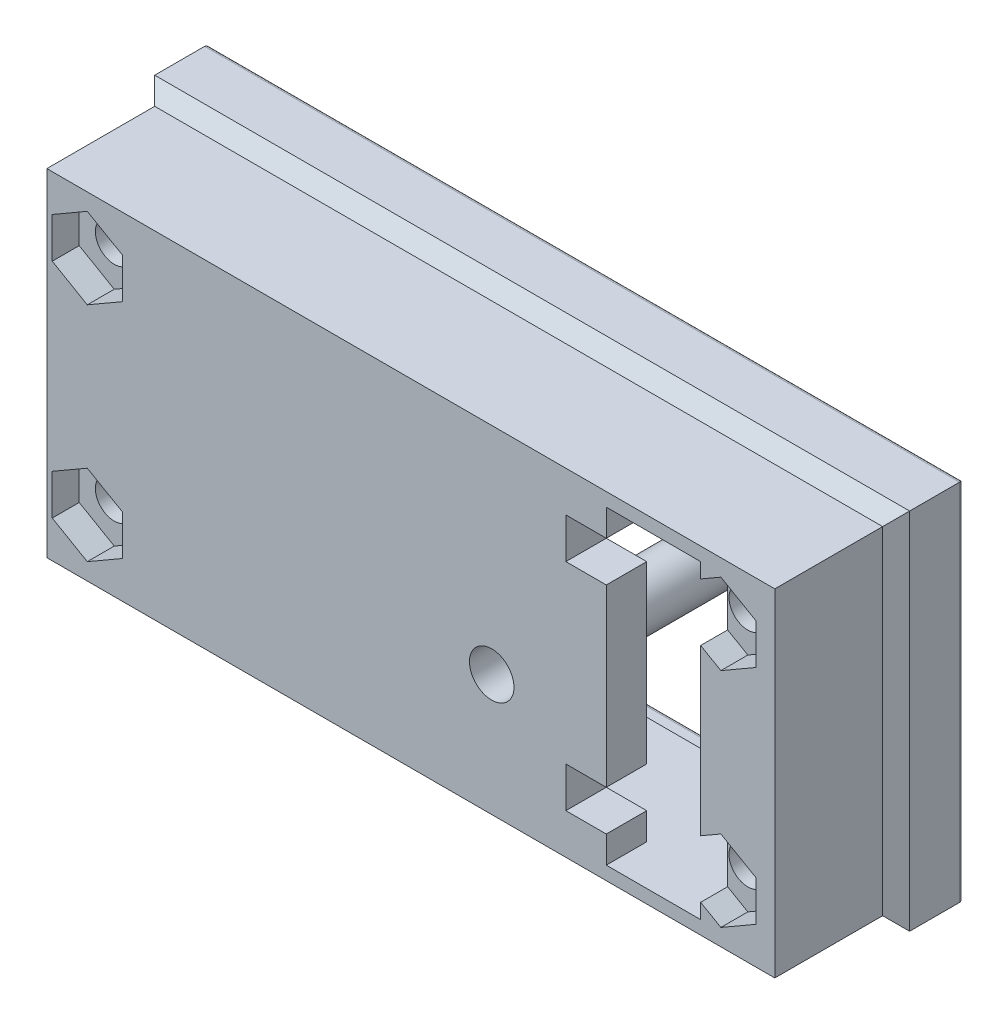
SolidWorks part; units mm, degrees
ref_plane "Front Plane" through (0, 0, 0) normal (0, 0, 1) x (1, 0, 0)
ref_plane "Top Plane" through (0, 0, 0) normal (0, 1, 0) x (1, 0, 0)
ref_plane "Right Plane" through (0, 0, 0) normal (1, 0, 0) x (0, 0, -1)
sketch "Sketch1" plane through (0, 0, 0) normal (0, 0, 1) x (1, 0, 0)
  line L1 (27, -12.5) -> (-27, -12.5)
  line L2 (27, -12.5) -> (27, 12.5)
  line L3 (27, 12.5) -> (-27, 12.5)
  line L4 (-27, -12.5) -> (-27, 12.5)
  line L5 (27, -12.5) -> (-27, 12.5) construction
  line L6 (27, 12.5) -> (-27, -12.5) construction
  line L7 (26, -11.5) -> (-26, -11.5)
  line L8 (26, -11.5) -> (26, 11.5)
  line L9 (26, 11.5) -> (-26, 11.5)
  line L10 (-26, -11.5) -> (-26, 11.5)
  line L11 (26, -11.5) -> (-26, 11.5) construction
  line L12 (26, 11.5) -> (-26, -11.5) construction
  point P0 (0, 0)
  point P6 (0, 0)
  dimension "D1" = 52
  dimension "D2" = 23
  dimension "D3" = 1
  dimension "D4" = 1
extrude "Boss-Extrude1" add sketch "Sketch1" along normal blind 8
sketch "Sketch2" plane through (0, 0, 8) normal (0, 0, 1) x (1, 0, 0)
  line L1 (27, -12.5) -> (-27, -12.5)
  line L2 (27, -12.5) -> (27, 12.5)
  line L3 (27, 12.5) -> (-27, 12.5)
  line L4 (-27, -12.5) -> (-27, 12.5)
  line L5 (27, -12.5) -> (-27, 12.5) construction
  line L6 (27, 12.5) -> (-27, -12.5) construction
  point P0 (0, 0)
extrude "Boss-Extrude2" add sketch "Sketch2" along normal blind 3
sketch "Sketch4" plane through (0, 0, 8) normal (0, 0, -1) x (-1, 0, 0)
  line L0 (26, -11.5) -> (-26, -11.5) construction
  line L1 (-21.5, 11.5) -> (-14.5, 11.5)
  line L2 (-21.5, 11.5) -> (-21.5, -11.5)
  line L3 (-21.5, -11.5) -> (-14.5, -11.5)
  line L4 (-14.5, 11.5) -> (-14.5, -11.5)
  line L5 (26, 11.5) -> (26, -11.5) construction
  line L6 (-26, 11.5) -> (26, 11.5) construction
  dimension "D1" = 7
  dimension "D2" = 40.5
extrude "Cut-Extrude1" cut sketch "Sketch4" against normal blind 3
sketch "Sketch5" plane through (0, 0, 8) normal (0, 0, -1) x (-1, 0, 0)
  circle A0 centre (-10, 0) radius 2
  dimension "D1" = 4
  dimension "D2" = 10
extrude "Boss-Extrude3" add sketch "Sketch5" along normal blind 9.7
fillet "Fillet1" radius 2 1 edges at (12, 0, 8)
sketch "Sketch6" plane through (0, 0, 8) normal (0, 0, -1) x (-1, 0, 0)
  line L0 (24, 8.25) -> (24, -8.25) construction
  line L1 (26, 11.5) -> (26, -11.5) construction
  line L2 (-23, 8.25) -> (-23, -8.25) construction
  line L3 (-26, -11.5) -> (-26, 11.5) construction
  line L4 (-27, -12.5) -> (-27, 12.5) construction
  circle A0 centre (24, 8.25) radius 1.4
  circle A1 centre (24, -8.25) radius 1.4
  circle A2 centre (-23, 8.25) radius 1.4
  circle A3 centre (-23, -8.25) radius 1.4
  point P4 (24, 0)
  point P6 (0, 0)
  point P17 (-23, 0)
  dimension "D2" = 2.8
  dimension "D3" = 2.8
  dimension "D4" = 2
  dimension "D5" = 16.5
  dimension "D6" = 4
  dimension "D1" = 16.5
extrude "Cut-Extrude2" cut sketch "Sketch6" against normal blind 10
sketch "Sketch8" plane through (0, 0, 11) normal (0, 0, 1) x (1, 0, 0)
  line L1 (-26.6, 9.7511) -> (-26.6, 6.7489)
  line L2 (-26.6, 6.7489) -> (-24, 5.2478)
  line L3 (-24, 5.2478) -> (-21.4, 6.7489)
  line L4 (-21.4, 6.7489) -> (-21.4, 9.7511)
  line L5 (-21.4, 9.7511) -> (-24, 11.2522)
  line L6 (-24, 11.2522) -> (-26.6, 9.7511)
  line L7 (-24, -5.2478) -> (-26.6, -6.7489)
  line L8 (-26.6, -6.7489) -> (-26.6, -9.7511)
  line L9 (-26.6, -9.7511) -> (-24, -11.2522)
  line L10 (-24, -11.2522) -> (-21.4, -9.7511)
  line L11 (-21.4, -9.7511) -> (-21.4, -6.7489)
  line L12 (-21.4, -6.7489) -> (-24, -5.2478)
  line L13 (23, 11.2522) -> (20.4, 9.7511)
  line L14 (-27, 12.5) -> (-27, -12.5) construction
  line L15 (20.4, 9.7511) -> (20.4, 6.7489)
  line L16 (20.4, 6.7489) -> (23, 5.2478)
  line L17 (23, 5.2478) -> (25.6, 6.7489)
  line L18 (25.6, 6.7489) -> (25.6, 9.7511)
  line L19 (25.6, 9.7511) -> (23, 11.2522)
  line L20 (23, -5.2478) -> (20.4, -6.7489)
  line L21 (20.4, -6.7489) -> (20.4, -9.7511)
  line L22 (20.4, -9.7511) -> (23, -11.2522)
  line L23 (23, -11.2522) -> (25.6, -9.7511)
  line L24 (25.6, -9.7511) -> (25.6, -6.7489)
  line L25 (25.6, -6.7489) -> (23, -5.2478)
  circle A0 centre (-24, 8.25) radius 2.6 construction
  circle A1 centre (-24, -8.25) radius 2.6 construction
  circle A2 centre (23, 8.25) radius 2.6 construction
  circle A3 centre (23, -8.25) radius 2.6 construction
  dimension "D2" = 5.2
extrude "Cut-Extrude3" cut sketch "Sketch8" against normal blind 2
sketch "Sketch10" plane through (0, 0, 8) normal (0, 0, -1) x (-1, 0, 0)
  line L1 (26, 11.5) -> (17.3098, 11.5)
  line L2 (26, 11.5) -> (26, 3.9581)
  line L3 (26, 3.9581) -> (17.3098, 3.9581)
  line L4 (17.3098, 11.5) -> (17.3098, 3.9581)
  line L5 (26, -11.5) -> (16.8129, -11.5)
  line L6 (26, -11.5) -> (26, -4.0462)
  line L7 (26, -4.0462) -> (16.8129, -4.0462)
  line L8 (16.8129, -11.5) -> (16.8129, -4.0462)
  line L9 (-26, 11.5) -> (-20.6838, 11.5)
  line L10 (-26, 11.5) -> (-26, 4.9094)
  line L11 (-26, 4.9094) -> (-20.6838, 4.9094)
  line L12 (-20.6838, 11.5) -> (-20.6838, 4.9094)
  line L13 (-26, -11.5) -> (-20.0802, -11.5)
  line L14 (-26, -11.5) -> (-26, -4.507)
  line L15 (-26, -4.507) -> (-20.0802, -4.507)
  line L16 (-20.0802, -11.5) -> (-20.0802, -4.507)
  circle A0 centre (24, 8.25) radius 1.4
  circle A1 centre (24, -8.25) radius 1.4
  circle A2 centre (24, -8.25) radius 2.4
  circle A3 centre (24, 8.25) radius 2.4
  circle A4 centre (24, 8.25) radius 1.4 construction
  circle A5 centre (-23, 8.25) radius 1.4
  circle A6 centre (-23, 8.25) radius 2.4
  circle A7 centre (-23, -8.25) radius 1.4
  circle A8 centre (-23, -8.25) radius 2.4
  circle M13 centre (24, 8.25) radius 1.4
  circle M14 centre (24, -8.25) radius 1.4
  dimension "D1" = 1
  dimension "D2" = 1
sketch "Sketch11" plane through (0, 0, 8) normal (0, 0, -1) x (-1, 0, 0)
  line L0 (-14.5, -11.5) -> (-14.5, 11.5) construction
  line L1 (-14.5, 9.5) -> (-11.5, 9.5)
  line L2 (-14.5, 9.5) -> (-14.5, 6.5)
  line L3 (-14.5, 6.5) -> (-11.5, 6.5)
  line L4 (-11.5, 9.5) -> (-11.5, 6.5)
  line L5 (-26, 11.5) -> (26, 11.5) construction
  line L6 (-14.5, -6.5) -> (-11.5, -6.5)
  line L7 (-14.5, -6.5) -> (-14.5, -9.5)
  line L8 (-14.5, -9.5) -> (-11.5, -9.5)
  line L9 (-11.5, -6.5) -> (-11.5, -9.5)
  line L10 (26, -11.5) -> (-14.5, -11.5) construction
  line L13 (27, -12.5) -> (-27, -12.5) construction
  circle A0 centre (-6, -3.5) radius 1.65
  point P2 (0, 0)
  dimension "D1" = 3.3
  dimension "D6" = 9
  dimension "D7" = 8.5
  dimension "D2" = 3
  dimension "D3" = 3
  dimension "D4" = 2
  dimension "D5" = 2
extrude "Cut-Extrude4" cut sketch "Sketch11" against normal blind 10
extrude "Boss-Extrude5" add sketch "Sketch10" along normal blind 10 contours L2 A3 M13 | L6 A2 M14 region at (-25.9349, 8.25, 8) region at (-21.6651, -8.25, 8)
extrude "Boss-Extrude6" add sketch "Sketch10<5>" along normal blind 12.5 contours L10 A6 A5 | L14 A8 A7 region at (20.7511, 8.25, 8) region at (25.3321, -8.25, 8)
sketch "Sketch10<5>" plane through (0, 0, 8) normal (0, 0, -1) x (-1, 0, 0) same geometry as "Sketch10"
sketch "Sketch12" plane through (0, 0, 0) normal (0, 0, -1) x (-1, 0, 0)
  line L1 (-27, 12.5) -> (27, 12.5)
  line L2 (-27, 12.5) -> (-27, -12.5)
  line L3 (-27, -12.5) -> (27, -12.5)
  line L4 (27, 12.5) -> (27, -12.5)
  line L5 (-28, 13.5) -> (28, 13.5)
  line L6 (-28, 13.5) -> (-28, -13.5)
  line L7 (-28, -13.5) -> (28, -13.5)
  line L8 (28, 13.5) -> (28, -13.5)
  dimension "D1" = 1
  dimension "D2" = 1
  dimension "D3" = 1
  dimension "D4" = 1
extrude "Boss-Extrude7" add sketch "Sketch12" along normal blind 2 and the other way blind 2
sketch "Sketch14" plane through (0, 0, 8) normal (0, 0, -1) x (-1, 0, 0)
  line L0 (-14.5, -6.5) -> (-14.5, 6.5) construction
  line L1 (-6, -0.2668) -> (-8.8, -1.8834)
  line L2 (-8.8, -1.8834) -> (-8.8, -5.1166)
  line L3 (-8.8, -5.1166) -> (-6, -6.7332)
  line L4 (-6, -6.7332) -> (-3.2, -5.1166)
  line L5 (-3.2, -5.1166) -> (-3.2, -1.8834)
  line L6 (-3.2, -1.8834) -> (-6, -0.2668)
  line L7 (-6, 0.8879) -> (-9.8, -1.3061)
  line L8 (-9.8, -1.3061) -> (-9.8, -5.6939)
  line L9 (-9.8, -5.6939) -> (-6, -7.8879)
  line L10 (-6, -7.8879) -> (-2.2, -5.6939)
  line L11 (-2.2, -5.6939) -> (-2.2, -1.3061)
  line L12 (-2.2, -1.3061) -> (-6, 0.8879)
  circle A0 centre (-6, -3.5) radius 2.8 construction
  circle A1 centre (-6, -3.5) radius 3.8 construction
  dimension "D1" = 5.6
  dimension "D2" = 1
extrude "Boss-Extrude8" add sketch "Sketch14" along normal blind 3
fillet "Fillet2" radius 0.3 8 edges at (-27, 0, -2) (0, 12.5, -2) (27, 0, -2) (0, -12.5, -2) (0, 13.5, -2) (-28, 0, -2) (0, -13.5, -2) (28, 0, -2)
fillet "Fillet3" radius 0.3 12 edges at (8, 0, -1.7) (-21.6, -8.25, -2) (-26, -8.25, -2) (-25.4, -8.25, -2) (-21.6, 8.25, -2) (-26, 8.25, -2) (-25.4, 8.25, -2) (25.4, 8.25, -4.5) (21.6, 8.25, -4.5) (20.6, -8.25, -4.5) (21.6, -8.25, -4.5) (20.6838, 8.25, -4.5)
chamfer "Chamfer1" distance 1 angle 45 4 edges at (0, -12.5, 2) (27, 0, 2) (-27, 0, 2) (0, 12.5, 2)
